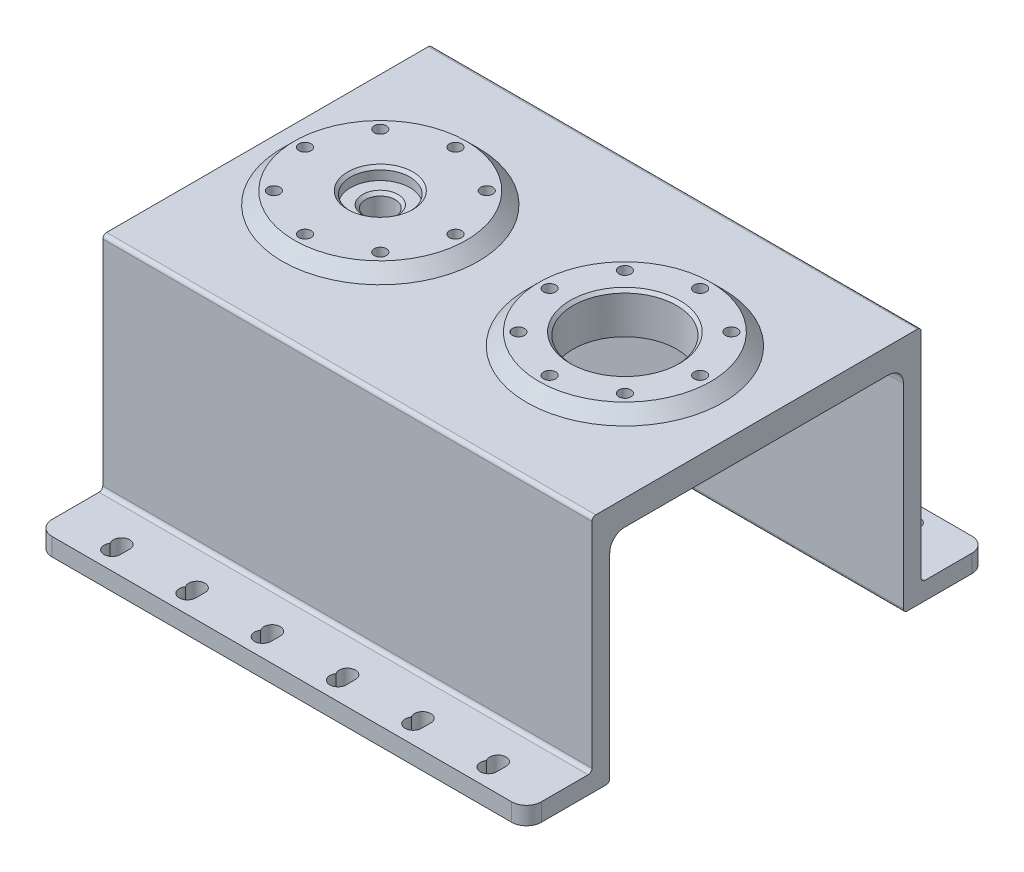
SolidWorks part; units mm, degrees
ref_plane "Front Plane" through (0, 0, 0) normal (0, 0, 1) x (1, 0, 0)
ref_plane "Top Plane" through (0, 0, 0) normal (0, 1, 0) x (1, 0, 0)
ref_plane "Right Plane" through (0, 0, 0) normal (1, 0, 0) x (0, 0, -1)
ref_axis "X axis" through (59.055, 0, 0) along (-1, 0, 0)
ref_axis "Y axis" through (0, 83.1148, 0) along (0, -1, 0)
sketch "PulleySketch" plane through (0, 0, 0) normal (0, 1, 0) x (1, 0, 0)
  line L0 (-86.4393, 9.5861) -> (-15.5572, 38.3445)
  line L1 (-72.2049, 0) -> (-41.3803, 0)
  line L2 (-79.7819, -9.9679) -> (-59.7359, -4.4011)
  line L3 (-30.8943, -27.5294) -> (-48.5801, -7.6819)
  circle A0 centre (0, 0) radius 41.3803
  circle A1 centre (-82.55, 0) radius 10.3451
  circle A2 centre (-56.7926, -15) radius 11
  point P12 (-56.7926, -4)
  point P17 (-92.8951, 0)
  point P18 (-56.7926, 0)
  point P19 (41.3803, 0)
  dimension "D3" = 82.55
  dimension "D1" = 82.7606
  dimension "D2" = 20.6901
  dimension "D4" = 22
  dimension "D5" = 4
  dimension "D9" = 76.4939
  dimension "D10" = 20.8046
  dimension "D12" = 26.5839
  dimension "D6" = 12.2627
  dimension "D7" = 19.0522
  dimension "D8" = 99.8807
  dimension "D11" = 12.2519
  dimension "D13" = 80.9492
sketch "WheelCenter" plane through (0, 0, 0) normal (1, 0, 0) x (0, 0, -1)
  line L0 (0, -15) -> (0, 0) construction
  point P0 (0, -15)
  dimension "D1" = 15
sketch "WheelClearance" plane through (0, 0, 0) normal (1, 0, 0) x (0, 0, -1)
  line L0 (0, -15) -> (-45.7905, -15) construction
  line L1 (-45.7905, -15) -> (-14.0894, 6.1341) construction
  line L2 (-14.0894, 6.1341) -> (0, -15) construction
  line L3 (0, 32.7905) -> (0, -62.7905)
  line L4 (-45.7905, -15) -> (-47.7905, -15) construction
  arc A0 (0, -62.7905) -> (0, 32.7905) centre (0, -15) cw
  point P10 (0, -15)
  dimension "D1" = 38.1
  dimension "D2" = 25.4
  dimension "D3" = 15
  dimension "D4" = 2
sketch "Sketch2" plane through (0, 0, 0) normal (1, 0, 0) x (0, 0, -1)
  line L0 (-77.6605, 0) -> (-55.5625, 0)
  line L1 (-55.5625, 0) -> (-55.5625, 74.676)
  line L2 (-55.5625, 74.676) -> (55.5625, 74.676)
  line L3 (55.5625, 74.676) -> (55.5625, 0)
  line L4 (55.5625, 0) -> (77.6605, 0)
  line L5 (77.6605, 0) -> (77.6605, -6)
  line L6 (77.6605, -6) -> (49.5625, -6)
  line L7 (49.5625, -6) -> (49.5625, 66.176)
  line L8 (49.5625, 66.176) -> (-49.5625, 66.176)
  line L9 (-49.5625, 66.176) -> (-49.5625, -6)
  line L10 (-49.5625, -6) -> (-77.6605, -6)
  line L11 (-77.6605, -6) -> (-77.6605, 0)
  line L12 (-91.9452, 74.676) -> (31.9599, 74.676) construction
  point P13 (0, 66.176)
  point P14 (0, 74.676)
  point P19 (-66.6115, 0)
  dimension "D1" = 8.5
  dimension "D3" = 111.125
  dimension "D4" = 74.676
  dimension "D5" = 6
  dimension "D6" = 6
  dimension "D2" = 22.098
extrude "Boss-Extrude1" add sketch "Sketch2" along normal blind 44.45 and the other way blind 120.65 contours L1 L2 L3 L4 L5 L6 L7 L8 L9 L10 L11 L0
sketch "Sketch5" plane through (-120.65, 0, 0) normal (-1, 0, 0) x (0, 0, 1)
  line L1 (-49.5625, -6) -> (49.5625, -6)
  line L2 (-49.5625, -6) -> (-49.5625, 66.176)
  line L3 (-49.5625, 66.176) -> (49.5625, 66.176)
  line L4 (49.5625, -6) -> (49.5625, 66.176)
extrude "Boss-Extrude2" add sketch "Sketch5" against normal blind 1.5
sketch "Sketch4" plane through (0, 0, 0) normal (0, 1, 0) x (1, 0, 0)
  line L0 (-120.65, 68.2625) -> (44.45, 68.2625) construction
  line L1 (-120.65, 55.5625) -> (-120.65, 77.6605) construction
  line L2 (44.45, 55.5625) -> (44.45, 77.6605) construction
  line L3 (-120.65, 71.4375) -> (44.45, 71.4375) construction
  line L4 (-101.6, 68.2625) -> (-101.6, 58.2625) construction
  line L5 (-127.0814, 55.5625) -> (61.3615, 55.5625) construction
  line L6 (-120.65, 55.5625) -> (44.45, 55.5625) construction
  line L7 (-101.6, 58.2625) -> (25.4, 58.2625) construction
  line L8 (-98.85, 68.2625) -> (-98.85, 71.4375)
  line L10 (-73.45, 68.2625) -> (-73.45, 71.4375)
  line L11 (-48.05, 68.2625) -> (-48.05, 71.4375)
  line L12 (-22.65, 68.2625) -> (-22.65, 71.4375)
  line L13 (2.75, 68.2625) -> (2.75, 71.4375)
  line L14 (28.15, 68.2625) -> (28.15, 71.4375)
  line L15 (-98.85, 68.2625) -> (-73.45, 68.2625) construction
  arc A22 (-103.8455, 69.85) -> (-98.85, 68.2625) centre (-101.6, 68.2625) ccw
  arc A23 (-103.8455, 69.85) -> (-98.85, 71.4375) centre (-101.6, 71.4375) cw
  arc A26 (-78.4455, 69.85) -> (-73.45, 71.4375) centre (-76.2, 71.4375) cw
  arc A27 (-78.4455, 69.85) -> (-73.45, 68.2625) centre (-76.2, 68.2625) ccw
  arc A28 (-53.0455, 69.85) -> (-48.05, 71.4375) centre (-50.8, 71.4375) cw
  arc A29 (-53.0455, 69.85) -> (-48.05, 68.2625) centre (-50.8, 68.2625) ccw
  arc A30 (-27.6455, 69.85) -> (-22.65, 71.4375) centre (-25.4, 71.4375) cw
  arc A31 (-27.6455, 69.85) -> (-22.65, 68.2625) centre (-25.4, 68.2625) ccw
  arc A32 (-2.2455, 69.85) -> (2.75, 71.4375) centre (0, 71.4375) cw
  arc A33 (-2.2455, 69.85) -> (2.75, 68.2625) centre (0, 68.2625) ccw
  arc A34 (23.1545, 69.85) -> (28.15, 71.4375) centre (25.4, 71.4375) cw
  arc A35 (23.1545, 69.85) -> (28.15, 68.2625) centre (25.4, 68.2625) ccw
  point P9 (-38.1, 68.2625)
  point P25 (-38.1, 58.2625)
  dimension "D2" = 2.75
  dimension "D1" = 12.7
  dimension "D6" = 127
  dimension "D5" = 15.875
  dimension "D7" = 10
  dimension "D4" = 25.4
  dimension "D3" = 6
extrude "Cut-Extrude1" cut sketch "Sketch4" against normal blind 101.6
mirror "Mirror1" about plane through (0, 0, 0) normal (0, 0, 1) of "Cut-Extrude1"
sketch "Sketch12" plane through (0, 74.676, 0) normal (0, 1, 0) x (1, 0, 0)
  circle A0 centre (0, 0) radius 29
  dimension "D1" = 58
extrude "Boss-Extrude3" add sketch "Sketch12" along normal blind 4.1
chamfer "Chamfer1" distance 4.1 angle 45 1 edges at (0, 74.676, 29)
sketch "Sketch10" plane through (0, 0, 0) normal (0, 1, 0) x (1, 0, 0)
  line L0 (0, 0) -> (17.9605, 17.9605) construction
  line L1 (0, 0) -> (54.5329, 0) construction
  circle A1 centre (17.9605, 17.9605) radius 2.05
  circle A2 centre (25.4, 0) radius 2.05
  circle A3 centre (17.9605, -17.9605) radius 2.05
  circle A4 centre (0, -25.4) radius 2.05
  circle A5 centre (-17.9605, -17.9605) radius 2.05
  circle A6 centre (-25.4, 0) radius 2.05
  circle A7 centre (-17.9605, 17.9605) radius 2.05
  circle A8 centre (0, 25.4) radius 2.05
  point P15 (0, 0)
  dimension "D2" = 4.1
  dimension "D3" = 25.4
  dimension "D4" = 45
  dimension "D5" = 8
extrude "Cut-Extrude2" cut sketch "Sketch10" against normal through all and the other way through all
sketch "Sketch17" plane through (0, 66.176, 0) normal (0, -1, 0) x (1, 0, 0)
  circle A0 centre (0, 0) radius 19.05
  dimension "D1" = 38.1
extrude "Boss-Extrude4" add sketch "Sketch17" along normal blind 9.652 from surface starting at face at (0, 74.676, -33.1)
sketch "Sketch13" plane through (0, 0, 0) normal (0, 1, 0) x (1, 0, 0)
  circle A0 centre (0, 0) radius 17.4625
  dimension "D1" = 34.925
extrude "Cut-Extrude4" cut sketch "Sketch13" along normal through all
chamfer "Chamfer3" distance 1 angle 45 1 edges at (0, 66.176, 19.05)
sketch "Sketch11" plane through (0, 0, 0) normal (0, 1, 0) x (1, 0, 0)
  circle A0 centre (0, 0) radius 16
  dimension "D1" = 32
extrude "Cut-Extrude3" [suppressed] cut sketch "Sketch11" along normal blind 1.75 from surface
pattern_linear "LPattern1" count 2 spacing 82.55 along (-1, 0, 0) of "Cut-Extrude2", "Chamfer1", "Boss-Extrude3"
sketch "Sketch14" plane through (0, 0, 0) normal (0, 1, 0) x (1, 0, 0)
  line L0 (0, 0) -> (-82.55, 0) construction
  circle A0 centre (-82.55, 0) radius 5
  dimension "D2" = 10
  dimension "D1" = 82.55
extrude "Cut-Extrude5" cut sketch "Sketch14" along normal through all
sketch "Sketch15" plane through (0, 78.776, 0) normal (0, 1, 0) x (1, 0, 0)
  line L0 (0, 0) -> (-82.55, 0) construction
  circle A0 centre (-82.55, 0) radius 10
  dimension "D1" = 82.55
  dimension "D2" = 20
extrude "Cut-Extrude6" cut sketch "Sketch15" against normal blind 4.1
chamfer "Chamfer2" [suppressed] distance 0.8 angle 45
fillet "Fillet1" radius 1.27 6 edges at (-38.1, 74.676, -55.5625) (-38.1, 74.676, 55.5625) (-38.1, 0, -55.5625) (-37.35, -6, -49.5625) (-37.35, -6, 49.5625) (-38.1, 0, 55.5625)
fillet "Fillet4" [suppressed] radius 1.5
fillet "Fillet3" radius 5 11 edges at (-37.35, 66.176, 49.5625) (-37.35, 66.176, -49.5625) (-119.15, -5.628, -49.9345) (-119.15, -5.628, 49.9345) (44.45, -3, -77.6605) (44.45, -3, 77.6605) (-120.65, -3, 77.6605) (-119.15, 30.723, -49.5625) (-119.15, 30.723, 49.5625) (-119.15, 66.176, 0) (-120.65, -3, -77.6605)
chamfer "Chamfer4" distance 1 angle 45 4 edges at (-82.55, 66.176, 5) (-82.55, 74.676, 5) (-82.55, 78.776, 10) (0, 78.776, 17.4625)
sketch "Sketch19" plane through (0, 0, 0) normal (1, 0, 0) x (0, 0, -1)
  line L0 (-112.0101, 65.024) -> (119.6828, 65.024) construction
  line L2 (30, 66.176) -> (30, 62.1218)
  line L3 (30, 62.1218) -> (40, 62.8211)
  line L4 (40, 62.8211) -> (40, 66.176)
  line L5 (30, 66.176) -> (40, 66.176)
  line L6 (0, 60.024) -> (43.4292, 60.024) construction
  line L7 (-6, 66.176) -> (6, 66.176) construction
  line L8 (-17.4625, 65.024) -> (17.4625, 65.024) construction
  point P6 (0, 60.024)
  dimension "D1" = 5
  dimension "D2" = 4
  dimension "D3" = 30
  dimension "D4" = 40
revolve "Revolve1" add sketch "Sketch19" angle 360 about axis through (0, 83.1148, 0) along (0, -1, 0)
chamfer "Chamfer5" distance 3 angle 40 1 edges at (0, 66.176, 40) first distance on face at (0, 66.176, 40)
fillet "Fillet5" [suppressed] radius 2
equation "\"D4@Sketch2\"=2.94in"
equation "\"D1@Boss-Extrude1\"=1.75in"
equation "\"D1@Fillet1\"=0.05in"
equation "\"D2@Boss-Extrude1\"=4.75in"
equation "\"D1@Sketch4\"=0.5in"
equation "\"D3@Sketch2\"=4.375in"
equation "\"D6@Sketch4\"=\"D4@Sketch4\"*(\"D3@Sketch4\"-1)"
equation "\"D2@Sketch2\"=0.87in"
equation "\"D5@Sketch4\"=0.625in"
equation "\"WheelDiam\"= 3in"
equation "\"WheelWidth\"= 2in"
equation "\"D2@WheelClearance\" = \"WheelWidth\" / 2"
equation "\"D1@WheelClearance\" = \"WheelDiam\" / 2"
equation "\"D3@Sketch10\"=2in/2"
equation "\"DistBetweenMotors\" = 3.25in"
equation "\"D3@LPattern1\"=\"DistBetweenMotors\""
equation "\"D1@Sketch14\"=\"DistBetweenMotors\""
equation "\"D1@Sketch15\"=\"DistBetweenMotors\""
equation "\"MotorDepthIn\"= 4.1"
equation "\"D1@Boss-Extrude3\"=\"MotorDepthIn\""
equation "\"D1@Chamfer1\"=\"MotorDepthIn\""
equation "\"D1@Cut-Extrude6\"= \"MotorDepthIn\""
equation "\"OriginToWheelCenter\"=15"
equation "\"D1@WheelCenter\"=\"OriginToWheelCenter\""
equation "\"D3@WheelClearance\"=\"OriginToWheelCenter\""
equation "\"D2@Sketch4\"=5.5/2"
equation "\"D1@Sketch13\"=1.375in"
equation "\"D1@Sketch17\"=1.5in"
equation "\"D1@Boss-Extrude4\"=0.38in"
equation "\"D3@PulleySketch\" = \"DistBetweenMotors\""
equation "\"PulleyMinWidth\"= ( \"D6@PulleySketch\" + \"D9@PulleySketch\" + \"D13@PulleySketch\" ) * 2"
equation "\"PulleyMaxWidth\"= ( \"D7@PulleySketch\" + \"D10@PulleySketch\" + \"D11@PulleySketch\" + \"D12@PulleySketch\" + \"D8@PulleySketch\" ) * 2"
